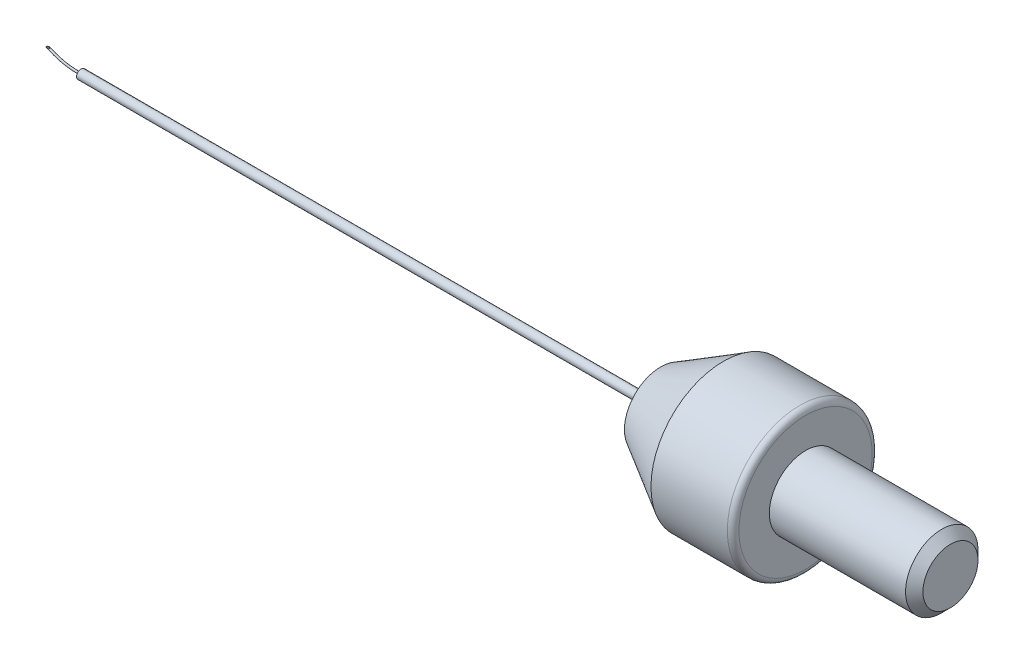
SolidWorks part; units mm, degrees
ref_plane "Vorne" through (0, 0, 0) normal (0, 0, 1) x (1, 0, 0)
ref_plane "Oben" through (0, 0, 0) normal (0, 1, 0) x (1, 0, 0)
ref_plane "Rechts" through (0, 0, 0) normal (1, 0, 0) x (0, 0, -1)
sketch "Skizze1" plane through (0, 0, 0) normal (0, 0, 1) x (1, 0, 0)
  line L0 (-27, 0.1545) -> (-7, 0.1545)
  line L1 (-7, 0.1545) -> (-7, 1.2495)
  line L2 (-7, 1.2495) -> (-4.8349, 2.4995)
  line L3 (-4.8349, 2.4995) -> (-2.2, 2.4995)
  line L4 (-2, 2.2995) -> (-2, 1.2495)
  line L5 (-2, 1.2495) -> (2.7, 1.2495)
  line L6 (3, 0.9495) -> (3, -0.0005)
  line L7 (3, -0.0005) -> (-9.5208, -0.0005) construction
  line L9 (0, -0.0005) -> (14.6759, -0.0005) construction
  line L10 (2.7, 1.2495) -> (3, 0.9495)
  line L11 (-7, 0.0495) -> (-27, 0.0495)
  line L12 (-7, 0.0495) -> (-7, -0.0005)
  line L13 (-7, -0.0005) -> (3, -0.0005)
  line L14 (-27, 0.1545) -> (-27, 0.0495)
  arc A0 (-2.2, 2.4995) -> (-2, 2.2995) centre (-2.2, 2.2995) cw
  point P7 (3, 1.2495)
  dimension "D9" = 0.2
  dimension "D1" = 2.5
  dimension "D2" = 5
  dimension "D3" = 5
  dimension "D4" = 30
  dimension "D6" = 2.5
  dimension "D7" = 5
  dimension "D8" = 20
  dimension "2" = 0.31
  dimension "D10" = 0.05
revolve "Rotation1" add sketch "Skizze1" angle 360 about L9
sketch "Skizze2" plane through (-2, 0, 0) normal (1, 0, 0) x (0, 0, -1)
  circle A0 centre (0, -0.0005) radius 2.5 construction
  circle A1 centre (0, -0.0005) radius 2.5
curve "Spirale/Helix1" [suppressed] pitch 25 height 7 turns 0.28
sketch "Skizze3" plane through (-2, 0, 0) normal (1, 0, 0) x (0, 0, -1)
  line L0 (2.5, 0.1) -> (2.5, -0.1)
  line L1 (2.5, -0.1) -> (2.4, 0)
  line L2 (2.4, 0) -> (2.5, 0.1)
  line L3 (2.4, 0) -> (2.5, 0) construction
  dimension "D1" = 90
  dimension "D2" = 0.1
sweep "Schnitt-Austragung1" [suppressed] cut profiles "Skizze3" path "Spirale/Helix1"
pattern_circular "Kreismuster1" [suppressed] count 35 over 360 of bodies 102
ref_plane "Ebene1" through (-4.5, 0, 0) normal (-1, 0, 0) x (0, 0, 1)
mirror "Spiegeln1" [suppressed] about plane through (-4.5, 0, 0) normal (-1, 0, 0)
sketch "草图1" plane through (-27, 0, 0) normal (-1, 0, 0) x (0, 0, 1)
  circle A0 centre (0, 0) radius 0.035
  circle A1 centre (0, 0) radius 0.025
  dimension "D1" = 0.07
  dimension "D2" = 0.05
sketch "草图3" plane through (0, 0, 0) normal (0, 0, 1) x (1, 0, 0)
  line L0 (-27, 0.025) -> (-27, -0.025) construction
  spline S1 degree 2 poles (-27, 0) (-27.6255, -0.022) (-28.1838, 0.2567) knots 0 0 0 1 1 1
  point P1 (-14.1587, 0.0031)
  point P5 (-27.1592, -0.0031)
  point P9 (-27, -0.0065)
  point P12 (-27, 0)
sweep "扫描1" add profiles "草图1" path "草图3"
sketch "草图4" plane through (0, 0, 0) normal (0, 0, 1) x (1, 0, 0)
  line L10 (-28.2005, 0.226) -> (-28.1671, 0.2874)
  line L11 (-28.1671, 0.2874) -> (-28.066, 0.2398)
  line L12 (-28.066, 0.2398) -> (-28.2005, 0.226)
  spline S1 degree 3 poles (-27, 0.035) (-27.0071, 0.0348) (-27.0211, 0.0343) (-27.0542, 0.0335) (-27.1705, 0.0325) (-27.3275, 0.0415) (-27.5215, 0.0696) (-27.6835, 0.1044) (-27.8556, 0.1551) (-27.9924, 0.2072) (-28.077, 0.2445) (-28.1115, 0.2605) (-28.1296, 0.2691) (-28.1482, 0.2781) (-28.1607, 0.2843) (-28.1671, 0.2874) knots 0 0 0 0 0.017675 0.034733 0.082253 0.306862 0.425164 0.569077 0.718639 0.870714 0.932602 0.948691 0.965284 0.982386 1 1 1 1 construction
  point P3 (-28.2005, 0.226)
  point P4 (-28.1671, 0.2874)
  point P5 (-28.066, 0.2398)
extrude "切除-拉伸1" cut sketch "草图4" along normal through all both and the other way through all
